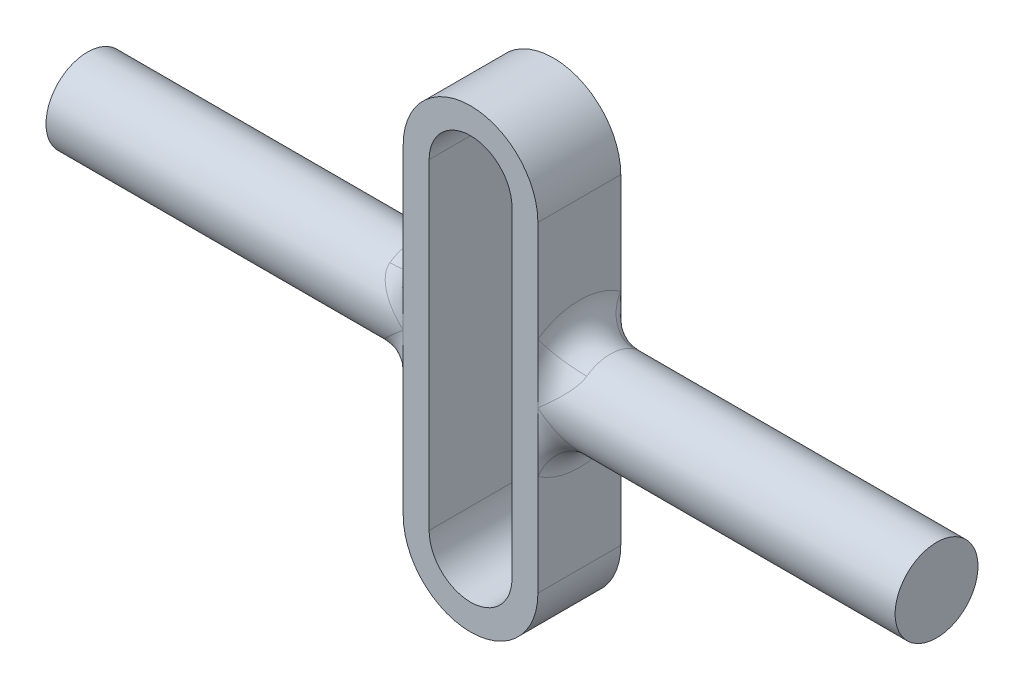
SolidWorks part; units mm, degrees
ref_plane "Front Plane" through (0, 0, 0) normal (0, 0, 1) x (1, 0, 0)
ref_plane "Top Plane" through (0, 0, 0) normal (0, 1, 0) x (1, 0, 0)
ref_plane "Right Plane" through (0, 0, 0) normal (1, 0, 0) x (0, 0, -1)
sketch "Sketch1" plane through (0, 0, 0) normal (0, 0, 1) x (1, 0, 0)
  line L0 (-3.1786, -10.5293) -> (-6.2318, -20.6433) construction
  line L2 (6.5342, -15.4952) -> (6.5342, 15.4952)
  line L4 (-6.4658, -15.5048) -> (-6.4658, 15.5048)
  line L5 (6.1403, -20.6911) -> (3.1346, -10.5629) construction
  line L6 (6.3156, 20.9207) -> (4.0342, 13.3636) construction
  line L8 (4.0342, -15.5) -> (4.0342, 15.5)
  line L10 (-3.9658, -15.5) -> (-3.9658, 15.5)
  line L11 (2.3804, -10.5418) -> (-2.3804, 10.5418) construction
  line L12 (3.1604, 13.996) -> (0, 0) construction
  line L13 (0, 0) -> (-3.2059, 10.8032) construction
  line L14 (3.2624, 10.8068) -> (0, 0) construction
  line L15 (-3.9658, 13.3636) -> (-6.2116, 20.9314) construction
  arc A0 (4.0342, 15.5) -> (-3.9658, 15.5) centre (0.0342, 15.5) ccw
  arc A1 (-3.9658, -15.5) -> (4.0342, -15.5) centre (0.0342, -15.5) ccw
  arc A5 (6.5342, 15.4952) -> (-6.4658, 15.5048) centre (0.0342, 15.5) ccw
  arc A6 (-6.4658, -15.5048) -> (6.5342, -15.4952) centre (0.0342, -15.5) ccw
  point P0 (0, 0)
  point P6 (0, 0)
  point P23 (0.039, 22)
  point P28 (0.039, -22)
  dimension "D1" = 8
  dimension "D2" = 44
  dimension "D3" = 31
extrude "Boss-Extrude1" add sketch "Sketch1" along normal blind 8
sketch "Sketch2" plane through (0, 0, 8) normal (0, 0, 1) x (1, 0, 0)
  line L0 (-3.9658, 15.5) -> (-3.9658, -15.5) construction
  point P0 (-3.9658, 0)
sketch "Sketch4" plane through (-6.4658, 0, 0) normal (-1, 0, 0) x (0, 0, 1)
  line L0 (0, 0) -> (8, 0) construction
  line L1 (0, 15.5048) -> (0, -15.5048) construction
  circle A0 centre (4, 0) radius 4
extrude "Boss-Extrude2" add sketch "Sketch4" along normal blind 34.485
sketch "Sketch5" plane through (6.5342, 0, 0) normal (1, 0, 0) x (0, 0, -1)
  circle A0 centre (-4, 0) radius 4
extrude "Boss-Extrude3" add sketch "Sketch5" along normal blind 34.485
fillet "Fillet1" radius 3 4 edges at (-6.4658, -4, 4) (-6.4658, 4, 4) (6.5342, -4, 4) (6.5342, 4, 4)
